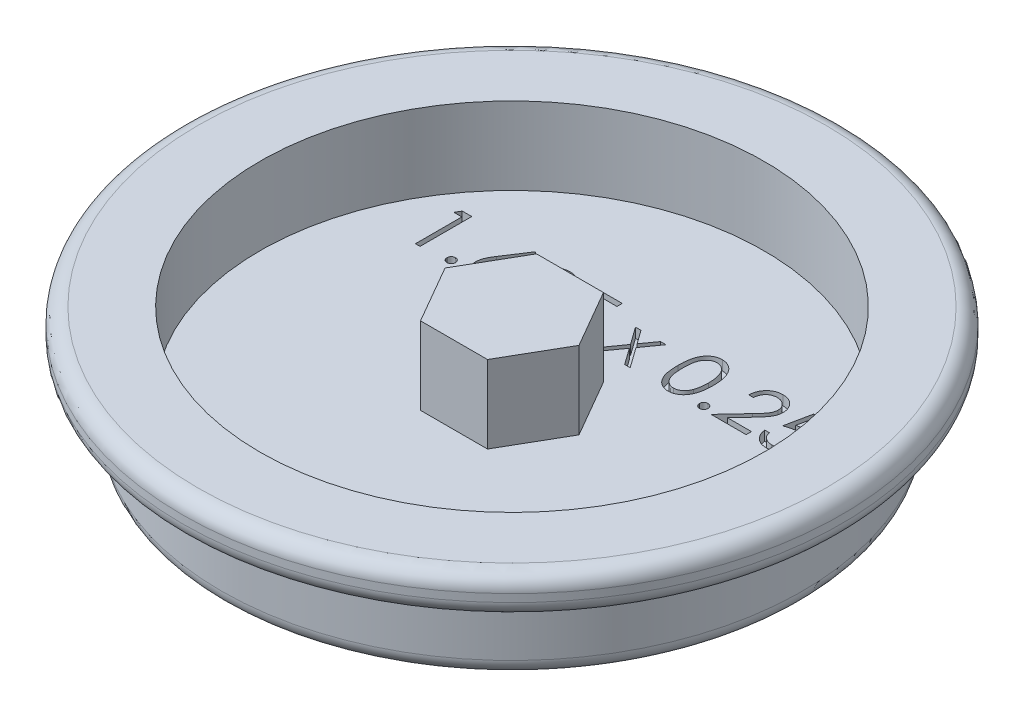
SolidWorks part; units mm, degrees
ref_plane "Front Plane" through (0, 0, 0) normal (0, 0, 1) x (1, 0, 0)
ref_plane "Top Plane" through (0, 0, 0) normal (0, 1, 0) x (1, 0, 0)
ref_plane "Right Plane" through (0, 0, 0) normal (1, 0, 0) x (0, 0, -1)
sketch "Sketch1" plane through (0, 0, 0) normal (0, 0, 1) x (1, 0, 0)
  line L0 (0, 0) -> (22.5425, 0)
  line L1 (23.8125, 1.27) -> (23.8125, 5.08)
  line L2 (25.0825, 6.35) -> (25.7175, 6.35)
  line L3 (26.9875, 7.62) -> (26.9875, 8.255)
  line L4 (25.7175, 9.525) -> (20.6375, 9.525)
  line L5 (20.6375, 9.525) -> (20.6375, 3.175)
  line L6 (20.6375, 3.175) -> (0, 3.175)
  line L7 (0, 3.175) -> (0, 0)
  arc A0 (26.9875, 8.255) -> (25.7175, 9.525) centre (25.7175, 8.255) ccw
  arc A1 (25.7175, 6.35) -> (26.9875, 7.62) centre (25.7175, 7.62) ccw
  arc A2 (23.8125, 5.08) -> (25.0825, 6.35) centre (25.0825, 5.08) cw
  arc A3 (22.5425, 0) -> (23.8125, 1.27) centre (22.5425, 1.27) ccw
  point P3 (0, 1.5875)
  dimension "D7" = 1.27
  dimension "D1" = 3.175
  dimension "D2" = 3.175
  dimension "D3" = 3.175
  dimension "D4" = 6.35
  dimension "D5" = 20.6375
  dimension "D6" = 6.35
revolve "Revolve1" add sketch "Sketch1" angle 360 about L7
sketch "Sketch2" plane through (0, 3.175, 0) normal (0, 1, 0) x (1, 0, 0)
  line L1 (2.7423, 4.7498) -> (-2.7423, 4.7498)
  line L2 (-2.7423, 4.7498) -> (-5.4846, 0)
  line L3 (-5.4846, 0) -> (-2.7423, -4.7498)
  line L4 (-2.7423, -4.7498) -> (2.7423, -4.7498)
  line L5 (2.7423, -4.7498) -> (5.4846, 0)
  line L6 (5.4846, 0) -> (2.7423, 4.7498)
  circle A0 centre (0, 0) radius 4.7498 construction
  dimension "D1" = 9.4996
extrude "Boss-Extrude1" add sketch "Sketch2" along normal blind 6.35
sketch "Sketch3" plane through (0, 3.175, 0) normal (0, 1, 0) x (1, 0, 0)
  text T0 "1.625 x 0.25" font "Century Gothic" height in points 16
  point P1 (-15.7485, 6.8622)
  point P2 (0, 0)
  point P3 (0, 0)
  point P4 (-16.2348, 6.8622)
extrude "Cut-Extrude1" cut sketch "Sketch3" against normal blind 0.7937
